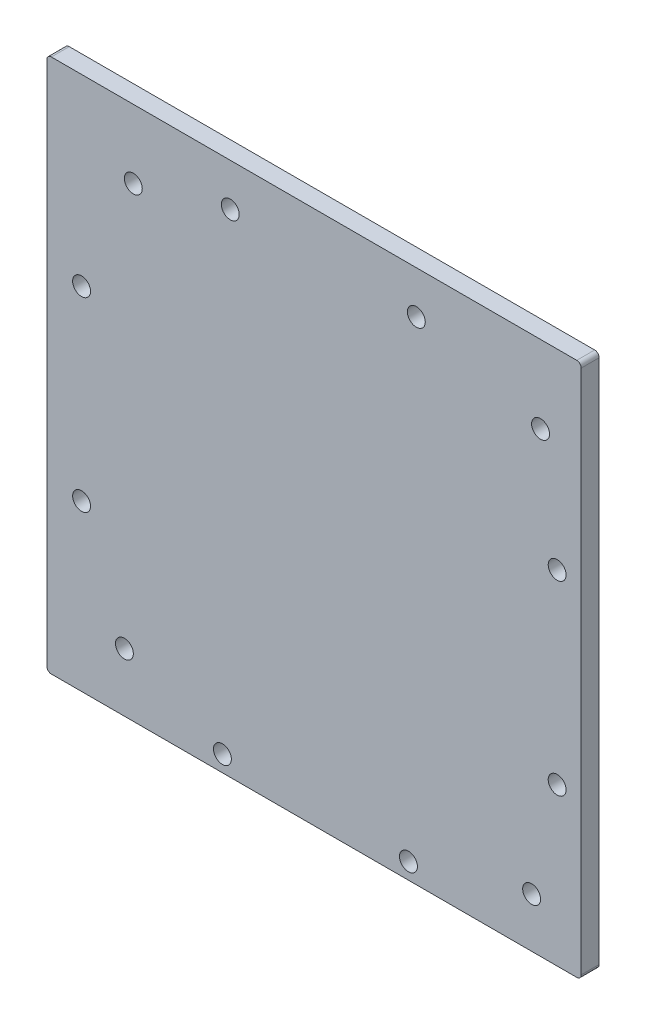
SolidWorks part; units mm, degrees
material "Acrylic (Medium-high impact)"
ref_plane "Front Plane" through (0, 0, 0) normal (0, 0, 1) x (1, 0, 0)
ref_plane "Top Plane" through (0, 0, 0) normal (0, 1, 0) x (1, 0, 0)
ref_plane "Right Plane" through (0, 0, 0) normal (1, 0, 0) x (0, 0, -1)
sketch "Sketch1" plane through (0, 0, 0) normal (0, 0, 1) x (1, 0, 0)
  line L1 (46.5772, -47.371) -> (-46.5773, -47.371)
  line L2 (47.371, -46.5773) -> (47.371, 46.5772)
  line L3 (46.5772, 47.371) -> (-46.5773, 47.371)
  line L4 (-47.371, -46.5773) -> (-47.371, 46.5772)
  line L5 (47.371, -47.371) -> (-47.371, 47.371) construction
  line L6 (47.371, 47.371) -> (-47.371, -47.371) construction
  arc A1 (-47.371, 46.5772) -> (-46.5773, 47.371) centre (-46.5773, 46.5772) cw
  arc A2 (46.5772, 47.371) -> (47.371, 46.5772) centre (46.5772, 46.5772) cw
  arc A3 (47.371, -46.5773) -> (46.5772, -47.371) centre (46.5772, -46.5773) cw
  arc A4 (-46.5773, -47.371) -> (-47.371, -46.5773) centre (-46.5773, -46.5773) cw
  point P2 (0, 0)
  dimension "D1" = 0.7937
  dimension "D2" = 94.742
extrude "Boss-Extrude1" add sketch "Sketch1" along normal blind 3.175
sketch "Sketch3" plane through (0, 0, 3.175) normal (0, 0, 1) x (1, 0, 0)
  circle A0 centre (16.7391, -44.4961) radius 1.5875 construction
  circle A1 centre (38.5743, -38.5743) radius 1.5875 construction
  circle A2 centre (43.1019, -19.5276) radius 1.5875 construction
  circle A3 centre (43.1019, 13.4568) radius 1.5875 construction
  circle A4 centre (40.1546, 33.6219) radius 1.5875 construction
  circle A5 centre (18.1334, 39.8196) radius 1.5875 construction
  circle A6 centre (-14.8511, 39.8196) radius 1.5875 construction
  circle A7 centre (-32.0416, 35.2021) radius 1.5875 construction
  circle A8 centre (-41.2139, 14.8511) radius 1.5875 construction
  circle A9 centre (-41.2139, -18.1334) radius 1.5875 construction
  circle A10 centre (-16.2454, -44.4961) radius 1.5875 construction
  circle A11 centre (-33.6219, -36.994) radius 1.5875 construction
  circle A12 centre (16.7391, -44.4961) radius 1.5875
  circle A13 centre (38.5743, -38.5743) radius 1.5875
  circle A14 centre (43.1019, -19.5276) radius 1.5875
  circle A15 centre (43.1019, 13.4568) radius 1.5875
  circle A16 centre (40.1546, 33.6219) radius 1.5875
  circle A17 centre (18.1334, 39.8196) radius 1.5875
  circle A18 centre (-14.8511, 39.8196) radius 1.5875
  circle A19 centre (-32.0416, 35.2021) radius 1.5875
  circle A20 centre (-41.2139, 14.8511) radius 1.5875
  circle A21 centre (-41.2139, -18.1334) radius 1.5875
  circle A22 centre (-16.2454, -44.4961) radius 1.5875
  circle A23 centre (-33.6219, -36.994) radius 1.5875
extrude "Cut-Extrude2" cut sketch "Sketch3" against normal up to next
